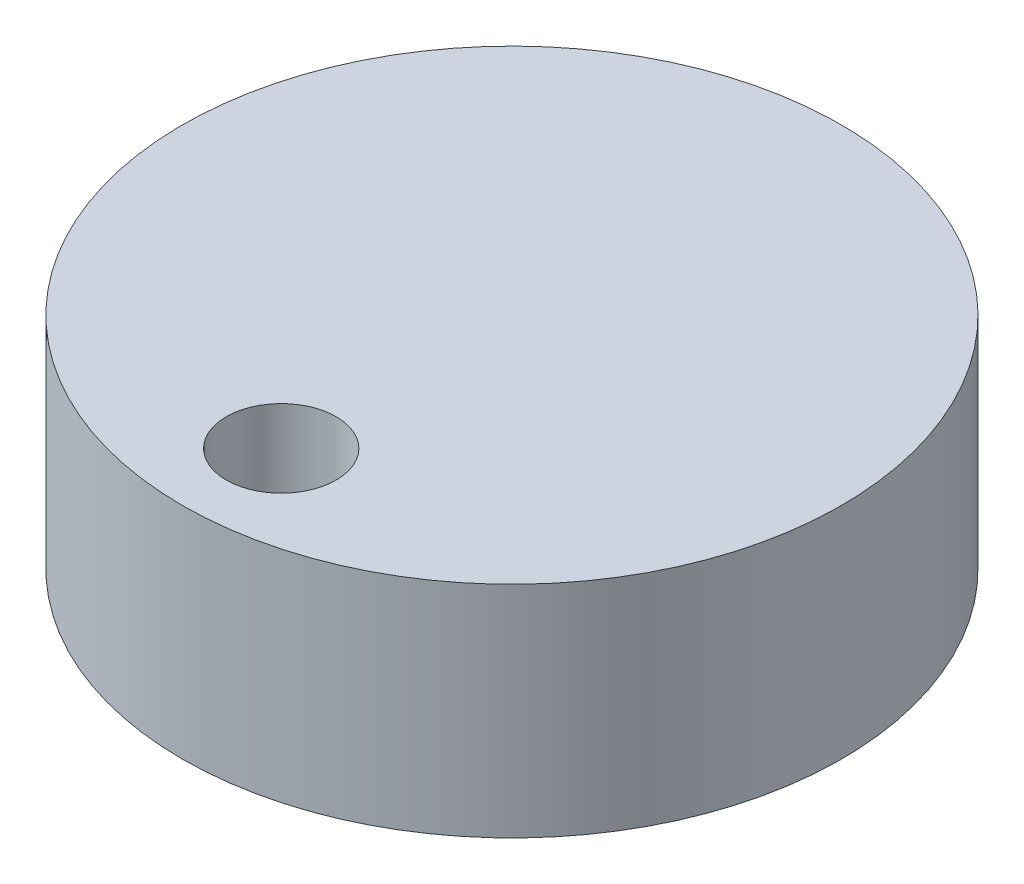
SolidWorks part; units mm, degrees
ref_plane "Front Plane" through (0, 0, 0) normal (0, 0, 1) x (1, 0, 0)
ref_plane "Top Plane" through (0, 0, 0) normal (0, 1, 0) x (1, 0, 0)
ref_plane "Right Plane" through (0, 0, 0) normal (1, 0, 0) x (0, 0, -1)
sketch "Sketch1" plane through (0, 0, 0) normal (0, 1, 0) x (1, 0, 0)
  line L0 (0, -5.715) -> (0, -3.175) construction
  line L1 (0, 3.175) -> (0, 32.385) construction
  circle A0 centre (0, 0) radius 3.175
  circle A1 centre (0, 13.335) radius 19.05
  dimension "D1" = 6.35
  dimension "D2" = 38.1
  dimension "D3" = 10.16
extrude "Boss-Extrude1" add sketch "Sketch1" along normal blind 6.35 and the other way blind 6.35
